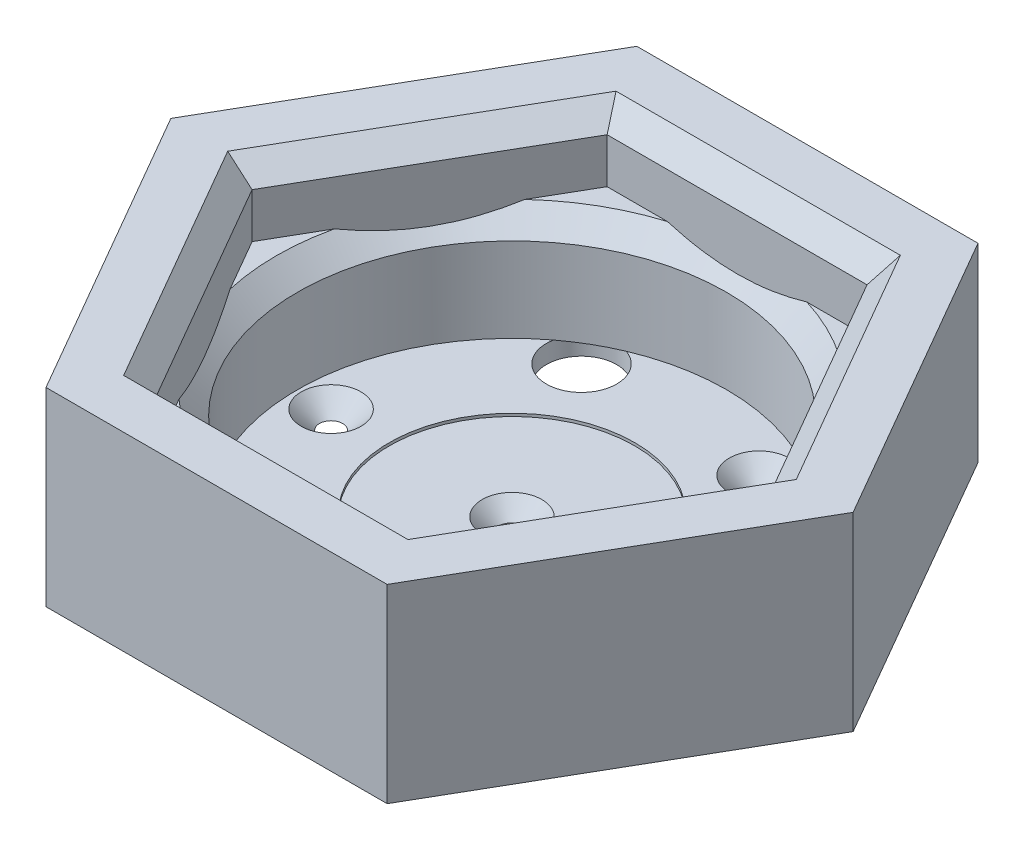
SolidWorks part; units mm, degrees
ref_plane "Front Plane" through (0, 0, 0) normal (0, 0, 1) x (1, 0, 0)
ref_plane "Top Plane" through (0, 0, 0) normal (0, 1, 0) x (1, 0, 0)
ref_plane "Right Plane" through (0, 0, 0) normal (1, 0, 0) x (0, 0, -1)
sketch "Sketch1" plane through (0, 0, 0) normal (0, 1, 0) x (1, 0, 0)
  line L0 (0, 0) -> (-24.2487, 42)
  line L1 (36.9504, 0) -> (18.4752, 32)
  line L2 (18.4752, 32) -> (-18.4752, 32)
  line L3 (-18.4752, 32) -> (-36.9504, 0)
  line L4 (-36.9504, 0) -> (-18.4752, -32)
  line L5 (-18.4752, -32) -> (18.4752, -32)
  line L6 (18.4752, -32) -> (36.9504, 0)
  line L7 (48.4974, 0) -> (24.2487, 42)
  line L8 (24.2487, 42) -> (-24.2487, 42)
  line L9 (-24.2487, 42) -> (-48.4974, 0)
  line L10 (-48.4974, 0) -> (-24.2487, -42)
  line L11 (-24.2487, -42) -> (24.2487, -42)
  line L12 (24.2487, -42) -> (48.4974, 0)
  line L13 (0, 0) -> (24.2487, 42)
  line L14 (0, 0) -> (48.4974, 0)
  circle A0 centre (0, 0) radius 32 construction
  circle A1 centre (0, 0) radius 42 construction
  circle A3 centre (12.8587, 22.272) radius 1.25
  circle A4 centre (-13.5, 23.3827) radius 5
  circle A5 centre (0, 0) radius 17.4625
  circle A6 centre (0, 0) radius 30.5
  circle A7 centre (12.8587, -22.272) radius 1.25
  circle A8 centre (-25.7174, 0) radius 1.25
  circle A9 centre (12.8587, -22.272) radius 1.25
  circle A10 centre (27, 0) radius 5
  circle A11 centre (-25.7174, 0) radius 1.25
  circle A12 centre (-13.5, -23.3827) radius 5
  circle A13 centre (0, 0) radius 1.25
  dimension "D1" = 10
  dimension "D2" = 34.925
  dimension "D3" = 10
  dimension "D4" = 2.5
  dimension "D6" = 61
  dimension "D9" = 2.5
  dimension "D5" = 64
  dimension "D7" = 3
  dimension "D8" = 3
extrude "Boss-Extrude1" add sketch "Sketch1" along normal blind 27 contours L14 L6 L5 L4 L3 L0 L9 L10 L11 L12 | L2 L13 L8 L0 | L1 L14 L7 L13 region at (-28.824, 0, -16.6416) region at (0, 0, -37.2252) region at (32.238, 0, -18.6126)
extrude "Boss-Extrude2" add sketch "Sketch1<5>" along normal blind 2.6 contours L13 A6 A4 L0 A5 A3 | A10 A6 L13 A3 A5 L14 | A12 A6 A10 L14 A5 L0 A4 A8 A7 | A6 L13 L2 L0 A4 | A12 A6 A4 L0 L3 L4 L5 L6 L14 A10 | A10 L14 L1 L13 A6 | A13 L13 A5 L0 | A13 L14 A5 L13 | A13 L0 A5 L14 region at (0, 0, -31.6263) region at (-18.0842, 0, -29.3676) region at (27.378, 0, -15.8067) region at (1.2808, 0, -23.3966) region at (-16.8684, 0, -18.6386) region at (19.6217, 0, -12.8075) region at (0, 0, -11.1701) region at (-2.4184, 0, 4.1888) region at (9.6736, 0, -5.5851)
sketch "Sketch1<5>" plane through (0, 0, 0) normal (0, 1, 0) x (1, 0, 0) same geometry as "Sketch1"
extrude "Boss-Extrude3" add sketch "Sketch1<6>" along normal blind 15 from surface contours A12 A6 A4 L0 L3 L4 L5 L6 L14 A10 | A10 L14 L1 L13 A6 | A6 L13 L2 L0 A4 | A6 A12 | A6 A10 L14 | L14 A10 A6 | A6 L0 A4 | A6 A4 L0 region at (0, 0, -31.6263) region at (-18.0842, 0, -29.3676) region at (-14.2612, 0, -27.6334) region at (-16.8006, 0, -26.1673) region at (27.378, 0, -15.8067) region at (-15.5309, 0, 26.9003) region at (31.0618, 0, 1.4661) region at (31.0618, 0, -1.4661) starting at face at (0, 2.6, 0)
sketch "Sketch1<6>" plane through (0, 0, 0) normal (0, 1, 0) x (1, 0, 0) same geometry as "Sketch1"
extrude "Cut-Extrude1" cut sketch "Sketch1<7>" against normal blind 0.4 from surface contours A5 starting at face at (12.8587, 2.6, 23.522)
sketch "Sketch1<7>" plane through (0, 0, 0) normal (0, 1, 0) x (1, 0, 0) same geometry as "Sketch1"
chamfer "Chamfer1" distance 3 angle 45 7 edges at (0, 17.6, 30.5) (27.7128, 27, 16) (0, 27, 32) (-27.7128, 27, 16) (-27.7128, 27, -16) (27.7128, 27, -16) (0, 27, -32)
chamfer "Chamfer2" distance 3 angle 45 4 edges at (12.8587, 2.6, -21.022) (-25.7174, 2.6, 1.25) (12.8587, 2.6, 23.522) (0, 2.2, 1.25)
